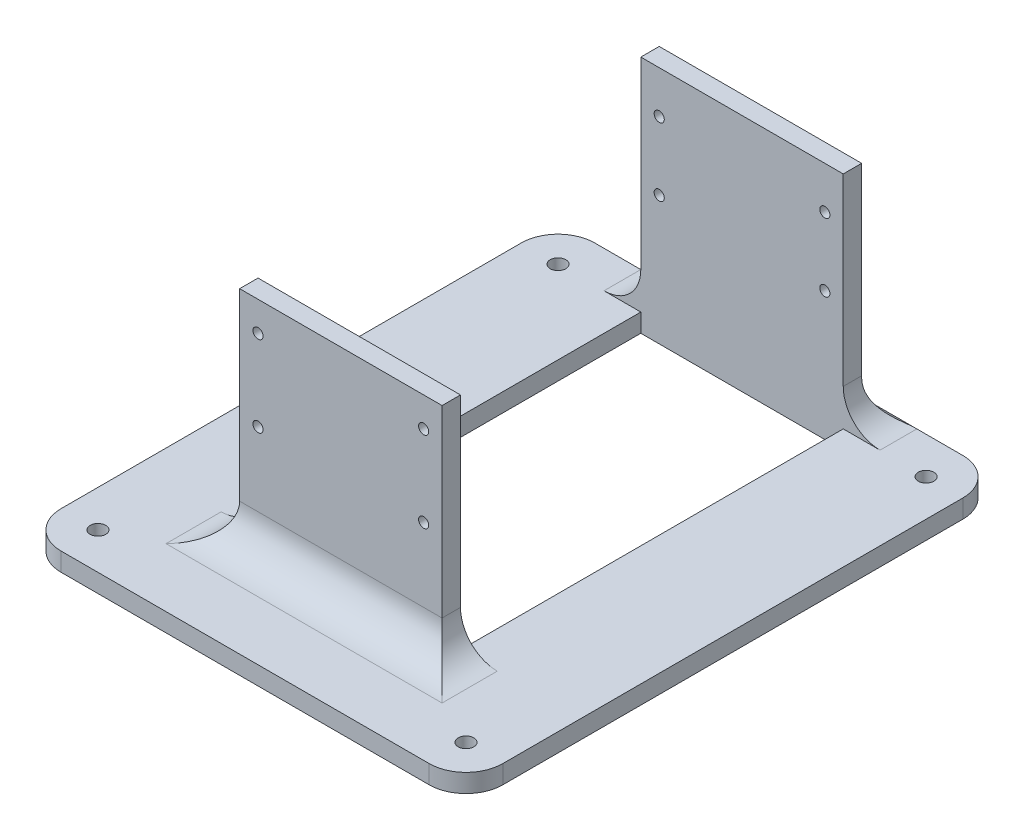
SolidWorks part; units mm, degrees
other "Markup1"
sketch "Sketch7" plane through (-69.5, 3, -80) normal (0, 1, 0) x (1, 0, 0)
sketch "Sketch8" plane through (-69.5, 5, -80) normal (0, 1, 0) x (1, 0, 0)
ref_plane "Front Plane" through (0, 0, 0) normal (0, 0, 1) x (1, 0, 0)
ref_plane "Top Plane" through (0, 0, 0) normal (0, 1, 0) x (1, 0, 0)
ref_plane "Right Plane" through (0, 0, 0) normal (1, 0, 0) x (0, 0, -1)
sketch "Sketch1" plane through (0, 0, 0) normal (0, 1, 0) x (1, 0, 0)
  line L1 (-60, 65) -> (60, 65)
  line L2 (-60, 65) -> (-60, -65)
  line L3 (-60, -65) -> (60, -65)
  line L4 (60, 65) -> (60, -65)
  line L5 (-60, 65) -> (60, -65) construction
  line L6 (-60, -65) -> (60, 65) construction
  point P0 (0, 0)
  dimension "D1" = 130
  dimension "D2" = 120
extrude "Boss-Extrude1" add sketch "Sketch1" along normal blind 5
sketch "Sketch10" plane through (0, 5, 0) normal (0, 1, 0) x (1, 0, 0)
  line L0 (-60, 65) -> (60, 65)
  line L1 (-60, 65) -> (-60, 80)
  line L2 (60, 65) -> (60, 80)
  line L3 (-60, 80) -> (60, 80)
  line L4 (60, 65) -> (-60, 65) construction
  line L5 (-60, 65) -> (-60, -65) construction
  line L6 (60, -65) -> (60, 65) construction
  dimension "D1" = 0
  dimension "D2" = 0
  dimension "D3" = 15
extrude "Boss-Extrude2" add sketch "Sketch10" against normal up to surface (5 mm away) up to face at (0, 0, 0)
sketch "Sketch9" plane through (0, 5, 0) normal (0, 1, 0) x (1, 0, 0)
  line L0 (0, -55) -> (0, 55) construction
  line L1 (-27.5, -34) -> (27.5, -34)
  line L2 (-27.5, -34) -> (-27.5, 70)
  line L3 (-27.5, 70) -> (27.5, 70)
  line L4 (27.5, -34) -> (27.5, 70)
  line L5 (-27.5, -34) -> (27.5, 70) construction
  line L6 (-27.5, 70) -> (27.5, -34) construction
  line L8 (60, 80) -> (-60, 80) construction
  point P0 (0, 18)
  dimension "D1" = 10
  dimension "D2" = 104
  dimension "D3" = 55
extrude "Cut-Extrude5" cut sketch "Sketch9" against normal through all
sketch "Sketch11" plane through (0, 5, 0) normal (0, 1, 0) x (1, 0, 0)
  line L0 (-27.5, 70) -> (27.5, 70)
  line L1 (-27.5, 70) -> (-27.5, 75)
  line L2 (27.5, 70) -> (27.5, 75)
  line L3 (-27.5, 75) -> (27.5, 75)
  line L4 (-27.5, -34) -> (27.5, -34)
  line L5 (-27.5, -34) -> (-27.5, -39)
  line L6 (27.5, -34) -> (27.5, -39)
  line L7 (-27.5, -39) -> (27.5, -39)
  dimension "D1" = 5
  dimension "D2" = 5
extrude "Boss-Extrude3" add sketch "Sketch11" along normal blind 60
sketch "Sketch12" plane through (0, 0, 39) normal (0, 0, 1) x (1, 0, 0)
  line L0 (-27.5, 5) -> (27.5, 5) construction
  line L1 (0, -55) -> (0, 55) construction
  circle A0 centre (-22.5, 35) radius 1.375
  circle A2 centre (22.5, 35) radius 1.375
  dimension "D3" = 2.75
  dimension "D1" = 30
  dimension "D2" = 22.5
extrude "Cut-Extrude6" cut sketch "Sketch12" against normal through all
sketch "Sketch13" plane through (0, 0, 39) normal (0, 0, 1) x (1, 0, 0)
  line L0 (0, -55) -> (0, 55) construction
  circle A0 centre (-22.5, 57) radius 1.375
  circle A1 centre (-22.5, 35) radius 1.375 construction
  circle A2 centre (22.5, 57) radius 1.375
  dimension "D2" = 2.75
  dimension "D1" = 22.5
  dimension "D3" = 22
extrude "Cut-Extrude7" cut sketch "Sketch13" against normal up to next
sketch "Sketch14" plane through (0, 0, -75) normal (0, 0, -1) x (-1, 0, 0)
  line L0 (-22.5, 35) -> (-22.5, 57.1524) construction
  line L1 (0, 55) -> (0, -55) construction
  circle A0 centre (-22.5, 53.5) radius 1.375
  circle A1 centre (22.5, 53.5) radius 1.375
  dimension "D2" = 2.75
  dimension "D1" = 18.5
extrude "Cut-Extrude8" cut sketch "Sketch14" against normal up to next
fillet "Fillet1" radius 10 1 edges at (0, 5, 39)
fillet "Fillet2" radius 10 1 edges at (0, 5, -75)
fillet "Fillet3" radius 10 4 edges at (27.5, 5, -75) (27.5, 5, 41.5) (-27.5, 5, 41.5) (-27.5, 5, -75)
sketch "Sketch16" plane through (0, 5, 0) normal (0, 1, 0) x (1, 0, 0)
  line L0 (-37.5, 80) -> (-60, 80) construction
  line L1 (-60, 80) -> (-60, -65) construction
  line L2 (-60, -65) -> (60, -65) construction
  line L3 (60, -65) -> (60, 80) construction
  circle A0 centre (-50, 70) radius 2.125
  circle A1 centre (-50, -55) radius 2.125
  circle A2 centre (50, -55) radius 2.125
  circle A3 centre (50, 70) radius 2.125
  dimension "D1" = 4.25
  dimension "D2" = 4.25
  dimension "D3" = 4.25
  dimension "D4" = 4.25
  dimension "D5" = 10
  dimension "D6" = 10
  dimension "D7" = 10
  dimension "D8" = 10
extrude "Cut-Extrude9" cut sketch "Sketch16" against normal blind 10
fillet "Fillet4" radius 10 4 edges at (-60, 2.5, -80) (60, 2.5, -80) (-60, 2.5, 65) (60, 2.5, 65)
